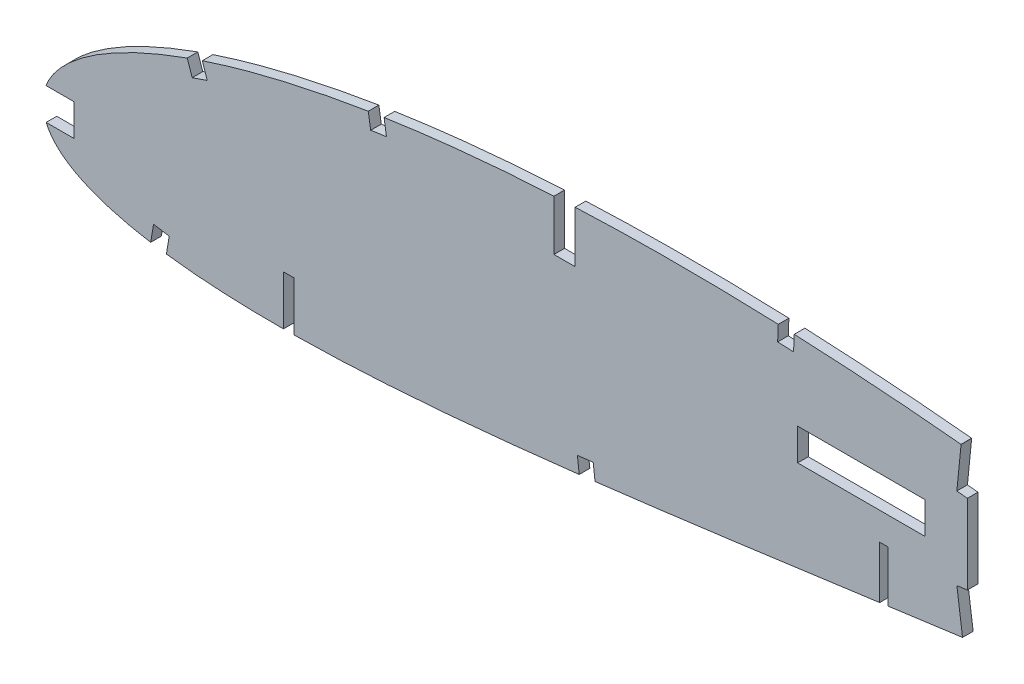
SolidWorks part; units mm, degrees
ref_plane "Front Plane" through (0, 0, 0) normal (0, 0, 1) x (1, 0, 0)
ref_plane "Top Plane" through (0, 0, 0) normal (0, 1, 0) x (1, 0, 0)
ref_plane "Right Plane" through (0, 0, 0) normal (1, 0, 0) x (0, 0, -1)
curve "Curve1"
  spline degree 3 poles (452.1031, 0.7048, 0) (452.0685, 0.7262, 0) (451.9301, 0.8117, 0) (451.6183, 1.003, 0) (451.099, 1.3216, 0) (450.372, 1.7653, 0) (449.438, 2.3329, 0) (448.2963, 3.0204, 0) (446.9478, 3.8257, 0) (445.3928, 4.7448, 0) (443.6314, 5.7736, 0) (441.6643, 6.9077, 0) (439.4916, 8.1409, 0) (437.1143, 9.468, 0) (434.5331, 10.8828, 0) (431.7485, 12.3789, 0) (428.7615, 13.9486, 0) (425.5733, 15.5853, 0) (422.1844, 17.2798, 0) (418.5964, 19.0251, 0) (414.8106, 20.8125, 0) (410.8282, 22.6325, 0) (406.6515, 24.4776, 0) (402.2816, 26.3365, 0) (397.7212, 28.201, 0) (392.972, 30.0605, 0) (388.0369, 31.9065, 0) (382.9178, 33.7272, 0) (377.6186, 35.5144, 0) (372.1418, 37.2567, 0) (366.4913, 38.9446, 0) (360.6704, 40.5671, 0) (354.684, 42.1159, 0) (348.5359, 43.5797, 0) (342.2312, 44.9487, 0) (335.775, 46.2147, 0) (329.1727, 47.3651, 0) (322.4425, 48.3989, 0) (315.6929, 49.2588, 0) (308.9571, 50.1023, 0) (302.2314, 50.8946, 0) (295.4235, 51.6533, 0) (288.5399, 52.3742, 0) (281.5875, 53.055, 0) (274.5733, 53.6928, 0) (267.5046, 54.2857, 0) (260.3883, 54.8303, 0) (253.2318, 55.3259, 0) (246.0422, 55.768, 0) (238.8272, 56.1563, 0) (231.5941, 56.4881, 0) (224.3504, 56.7611, 0) (217.1039, 56.9737, 0) (209.862, 57.1238, 0) (202.6326, 57.2105, 0) (195.4232, 57.2315, 0) (188.2416, 57.1863, 0) (181.0954, 57.0734, 0) (173.9924, 56.8912, 0) (166.9401, 56.6395, 0) (159.9462, 56.3182, 0) (153.0184, 55.9248, 0) (146.164, 55.4618, 0) (139.3909, 54.9271, 0) (132.7063, 54.3206, 0) (126.1174, 53.645, 0) (119.6314, 52.8983, 0) (113.2554, 52.0826, 0) (106.9962, 51.1996, 0) (100.8609, 50.2488, 0) (94.8561, 49.2329, 0) (88.9882, 48.153, 0) (83.2635, 47.0122, 0) (77.6882, 45.8109, 0) (72.2682, 44.5525, 0) (67.0092, 43.2395, 0) (61.9167, 41.874, 0) (56.9959, 40.4594, 0) (52.2519, 38.999, 0) (47.6902, 37.4943, 0) (43.3141, 35.951, 0) (39.1291, 34.3702, 0) (35.1384, 32.7568, 0) (31.3466, 31.113, 0) (27.7567, 29.4439, 0) (24.3726, 27.7512, 0) (21.1967, 26.0397, 0) (18.2324, 24.3122, 0) (15.4823, 22.5717, 0) (12.9477, 20.8227, 0) (10.632, 19.0664, 0) (8.5361, 17.307, 0) (6.6613, 15.5474, 0) (5.0102, 13.7886, 0) (3.5829, 12.0339, 0) (2.3811, 10.2847, 0) (1.4051, 8.5424, 0) (0.6571, 6.8085, 0) (0.1363, 5.084, 0) (-0.1488, 3.3712, 0) (-0.2197, 1.669, 0) (-0.0731, 0.5555, 0) (0, 0, 0) knots 0 0 0 0 0.000254 0.001015 0.002283 0.004057 0.006331 0.009105 0.012374 0.016134 0.02038 0.025106 0.030306 0.035972 0.0421 0.048678 0.055702 0.06316 0.071046 0.07935 0.088063 0.097176 0.106678 0.116562 0.126814 0.137428 0.148394 0.1597 0.171338 0.183298 0.19557 0.208144 0.221012 0.234162 0.247587 0.261277 0.275223 0.289414 0.303771 0.317689 0.331784 0.34604 0.360444 0.374983 0.38964 0.404403 0.419257 0.434187 0.449177 0.464215 0.479284 0.49437 0.509458 0.524532 0.539579 0.554583 0.56953 0.584403 0.599191 0.613877 0.628447 0.642889 0.657186 0.671326 0.685294 0.699078 0.712665 0.726043 0.739198 0.752118 0.764792 0.777208 0.789356 0.801224 0.812804 0.824083 0.835055 0.84571 0.856038 0.866034 0.875689 0.884998 0.893953 0.902553 0.910789 0.918661 0.926166 0.933303 0.940071 0.946475 0.952518 0.958205 0.963547 0.968557 0.97325 0.977651 0.981787 0.985694 0.989415 0.993001 0.996508 1 1 1 1
curve "Curve2"
  spline degree 3 poles (0, 0, 0) (0.1161, -0.5481, 0) (0.3488, -1.6467, 0) (0.9811, -3.2283, 0) (1.8173, -4.7487, 0) (2.8749, -6.2038, 0) (4.147, -7.5932, 0) (5.6306, -8.9184, 0) (7.3243, -10.1787, 0) (9.226, -11.3735, 0) (11.3328, -12.5041, 0) (13.6425, -13.5697, 0) (16.1528, -14.5701, 0) (18.8611, -15.5039, 0) (21.764, -16.3724, 0) (24.8588, -17.1737, 0) (28.1419, -17.9088, 0) (31.6103, -18.5759, 0) (35.26, -19.1755, 0) (39.0874, -19.7075, 0) (43.0885, -20.172, 0) (47.2594, -20.5682, 0) (51.596, -20.8969, 0) (56.0938, -21.1583, 0) (60.7487, -21.3533, 0) (65.556, -21.481, 0) (70.5112, -21.5436, 0) (75.6096, -21.5419, 0) (80.8464, -21.4754, 0) (86.2171, -21.3479, 0) (91.7164, -21.1586, 0) (97.3395, -20.9096, 0) (103.0813, -20.6036, 0) (108.9365, -20.2416, 0) (114.9002, -19.8251, 0) (120.967, -19.3576, 0) (127.1315, -18.8401, 0) (133.3883, -18.2757, 0) (139.7319, -17.6673, 0) (146.1567, -17.0167, 0) (152.6572, -16.327, 0) (159.2275, -15.6004, 0) (165.862, -14.8409, 0) (172.5546, -14.0497, 0) (179.2998, -13.2315, 0) (186.0911, -12.3877, 0) (192.923, -11.5217, 0) (199.7891, -10.6375, 0) (206.6832, -9.7349, 0) (213.5994, -8.8205, 0) (220.5311, -7.8935, 0) (227.4721, -6.9586, 0) (234.4161, -6.0188, 0) (241.3564, -5.0743, 0) (248.2868, -4.1291, 0) (255.2009, -3.1857, 0) (262.0918, -2.2442, 0) (268.9535, -1.3094, 0) (275.779, -0.3811, 0) (282.5619, 0.5389, 0) (289.2958, 1.4477, 0) (295.9744, 2.3443, 0) (302.5907, 3.228, 0) (309.138, 4.0992, 0) (315.5119, 4.9314, 0) (321.6955, 5.769, 0) (327.7099, 6.4556, 0) (333.6493, 7.0417, 0) (339.52, 7.5222, 0) (345.315, 7.9041, 0) (351.0275, 8.19, 0) (356.6509, 8.3839, 0) (362.1779, 8.4917, 0) (367.6017, 8.516, 0) (372.9148, 8.4647, 0) (378.1105, 8.3417, 0) (383.1813, 8.1528, 0) (388.1203, 7.9042, 0) (392.9205, 7.6027, 0) (397.5745, 7.2527, 0) (402.076, 6.8625, 0) (406.4179, 6.4377, 0) (410.5937, 5.9833, 0) (414.5972, 5.5086, 0) (418.4221, 5.0169, 0) (422.0625, 4.5163, 0) (425.5126, 4.0117, 0) (428.7669, 3.5097, 0) (431.8204, 3.015, 0) (434.6681, 2.5342, 0) (437.3055, 2.0718, 0) (439.7281, 1.6323, 0) (441.9324, 1.2212, 0) (443.9143, 0.8406, 0) (445.6709, 0.4968, 0) (447.199, 0.1913, 0) (448.4964, -0.0716, 0) (449.5609, -0.2909, 0) (450.3908, -0.463, 0) (450.9844, -0.5881, 0) (451.3411, -0.6626, 0) (451.4997, -0.6964, 0) (451.5393, -0.7048, 0) knots 0 0 0 0 0.003638 0.007293 0.011028 0.014901 0.018963 0.023258 0.027821 0.032679 0.037853 0.043362 0.049215 0.055422 0.061989 0.068918 0.076211 0.083868 0.091887 0.100266 0.109 0.118085 0.127515 0.137285 0.147388 0.157816 0.168563 0.179619 0.190977 0.202627 0.21456 0.226767 0.239236 0.251959 0.264924 0.27812 0.291536 0.30516 0.318981 0.332985 0.347163 0.361499 0.375981 0.390597 0.405333 0.420175 0.43511 0.450124 0.465203 0.480333 0.495501 0.51069 0.525887 0.541078 0.556247 0.571382 0.586466 0.601485 0.616424 0.631269 0.646007 0.660621 0.675098 0.689423 0.703582 0.716908 0.730009 0.742952 0.755726 0.76832 0.780724 0.792927 0.804916 0.816679 0.828204 0.839475 0.850481 0.861208 0.871639 0.881763 0.891564 0.901027 0.910139 0.918884 0.927249 0.935221 0.942785 0.949928 0.956638 0.962904 0.968712 0.974054 0.978918 0.983297 0.98718 0.990561 0.993433 0.995791 0.99763 0.998946 0.999737 1 1 1 1
sketch "Sketch1" plane through (0, 0, 0) normal (0, 0, 1) x (1, 0, 0)
  line L24 (435.3301, 0.6787) -> (439.1729, -1.6142)
  line L25 (434.7872, -0.6787) -> (439.1729, -1.6142)
  spline S4 degree 3 poles (0, 0) (0.1118, -0.5277) (0.3359, -1.5856) (0.9447, -3.1085) (1.7499, -4.5725) (2.7683, -5.9736) (3.9931, -7.3115) (5.4217, -8.5876) (7.0526, -9.8011) (8.8837, -10.9516) (10.9124, -12.0402) (13.1363, -13.0663) (15.5535, -14.0296) (18.1613, -14.9287) (20.9565, -15.765) (23.9365, -16.5366) (27.0978, -17.2444) (30.4375, -17.8867) (33.9519, -18.4641) (37.6373, -18.9763) (41.49, -19.4236) (45.5061, -19.8051) (49.6818, -20.1216) (54.0128, -20.3734) (58.4949, -20.5611) (63.1239, -20.6841) (67.8952, -20.7443) (72.8045, -20.7427) (77.847, -20.6787) (83.0184, -20.5559) (88.3137, -20.3736) (93.7282, -20.1339) (99.2569, -19.8392) (104.895, -19.4906) (110.6374, -19.0896) (116.4791, -18.6394) (122.4149, -18.1411) (128.4396, -17.5977) (134.5478, -17.0118) (140.7343, -16.3853) (146.9936, -15.7212) (153.3201, -15.0216) (159.7085, -14.2903) (166.1528, -13.5285) (172.6478, -12.7406) (179.1872, -11.9281) (185.7655, -11.0942) (192.377, -10.2428) (199.0153, -9.3738) (205.6749, -8.4933) (212.3494, -7.6007) (219.0329, -6.7005) (225.7193, -5.7955) (232.4021, -4.886) (239.0753, -3.9759) (245.7329, -3.0675) (252.3682, -2.161) (258.9753, -1.2608) (265.5476, -0.3669) (272.0789, 0.5189) (278.563, 1.394) (284.9937, 2.2573) (291.3645, 3.1082) (297.669, 3.9471) (303.8064, 4.7484) (309.7606, 5.555) (315.5518, 6.2161) (321.2709, 6.7805) (326.9238, 7.2431) (332.5038, 7.6108) (338.0044, 7.8861) (343.4191, 8.0729) (348.7411, 8.1767) (353.9637, 8.2001) (359.0797, 8.1506) (364.0826, 8.0323) (368.9653, 7.8503) (373.7211, 7.6109) (378.3431, 7.3206) (382.8245, 6.9836) (387.159, 6.6079) (391.3398, 6.1989) (395.3607, 5.7613) (399.2157, 5.3043) (402.8986, 4.8308) (406.404, 4.3487) (409.7261, 3.8629) (412.8597, 3.3795) (415.7999, 2.9031) (418.5419, 2.4402) (421.0815, 1.9949) (423.4142, 1.5717) (425.5368, 1.1759) (427.445, 0.8095) (429.1365, 0.4784) (430.6079, 0.1842) (431.8572, -0.0689) (432.8822, -0.2801) (433.6813, -0.4458) (434.2529, -0.5663) (434.5964, -0.638) (434.749, -0.6706) (434.7872, -0.6787) knots 0 0 0 0 0.003638 0.007293 0.011028 0.014901 0.018963 0.023258 0.027821 0.032679 0.037853 0.043362 0.049215 0.055422 0.061989 0.068918 0.076211 0.083868 0.091887 0.100266 0.109 0.118085 0.127515 0.137285 0.147388 0.157816 0.168563 0.179619 0.190977 0.202627 0.21456 0.226767 0.239236 0.251959 0.264924 0.27812 0.291536 0.30516 0.318981 0.332985 0.347163 0.361499 0.375981 0.390597 0.405333 0.420175 0.43511 0.450124 0.465203 0.480333 0.495501 0.51069 0.525887 0.541078 0.556247 0.571382 0.586466 0.601485 0.616424 0.631269 0.646007 0.660621 0.675098 0.689423 0.703582 0.716908 0.730009 0.742952 0.755726 0.76832 0.780724 0.792927 0.804916 0.816679 0.828204 0.839475 0.850481 0.861208 0.871639 0.881763 0.891564 0.901027 0.910139 0.918884 0.927249 0.935221 0.942785 0.949928 0.956638 0.962904 0.968712 0.974054 0.978918 0.983297 0.98718 0.990561 0.993433 0.995791 0.99763 0.998946 0.999737 1 1 1 1
  spline S5 degree 3 poles (435.3301, 0.6787) (435.2968, 0.6993) (435.1635, 0.7816) (434.8632, 0.9658) (434.3632, 1.2726) (433.6632, 1.6998) (432.7638, 2.2463) (431.6645, 2.9084) (430.3661, 3.6837) (428.8687, 4.5688) (427.1727, 5.5594) (425.2785, 6.6514) (423.1865, 7.8389) (420.8974, 9.1168) (418.4119, 10.4791) (415.7306, 11.9197) (412.8545, 13.4311) (409.7845, 15.0071) (406.5213, 16.6387) (403.0665, 18.3192) (399.4211, 20.0403) (395.5865, 21.7928) (391.5647, 23.5695) (387.357, 25.3594) (382.9657, 27.1547) (378.3927, 28.9452) (373.6407, 30.7228) (368.7116, 32.4759) (363.609, 34.1968) (358.3353, 35.8745) (352.8945, 37.4998) (347.2896, 39.0621) (341.5252, 40.5534) (335.6052, 41.9629) (329.5344, 43.2811) (323.3177, 44.5002) (316.9603, 45.6079) (310.4799, 46.6033) (303.9807, 47.4313) (297.4948, 48.2435) (291.0186, 49.0064) (284.4633, 49.737) (277.8351, 50.4311) (271.1406, 51.0867) (264.3866, 51.7008) (257.5802, 52.2717) (250.7279, 52.7961) (243.8369, 53.2733) (236.914, 53.699) (229.9667, 54.0729) (223.0019, 54.3924) (216.027, 54.6553) (209.0493, 54.86) (202.0761, 55.0045) (195.1149, 55.088) (188.173, 55.1082) (181.2578, 55.0647) (174.3767, 54.956) (167.5373, 54.7806) (160.7467, 54.5381) (154.0122, 54.2288) (147.3414, 53.85) (140.7414, 53.4041) (134.2195, 52.8893) (127.7829, 52.3053) (121.4385, 51.6548) (115.1931, 50.9357) (109.0536, 50.1503) (103.0266, 49.3001) (97.119, 48.3846) (91.3369, 47.4064) (85.6868, 46.3665) (80.1745, 45.2681) (74.806, 44.1113) (69.5871, 42.8996) (64.5231, 41.6353) (59.6196, 40.3205) (54.8814, 38.9584) (50.3134, 37.5521) (45.9209, 36.1032) (41.7071, 34.6172) (37.6774, 33.0951) (33.8348, 31.5415) (30.1837, 29.9587) (26.7269, 28.3515) (23.4684, 26.7216) (20.4104, 25.0737) (17.5559, 23.4102) (14.9079, 21.7343) (12.4673, 20.0502) (10.2376, 18.359) (8.2194, 16.6649) (6.4142, 14.9706) (4.8244, 13.2771) (3.45, 11.5875) (2.2928, 9.9031) (1.353, 8.2255) (0.6327, 6.5559) (0.1312, 4.8953) (-0.1433, 3.2462) (-0.2116, 1.607) (-0.0704, 0.5349) (0, 0) knots 0 0 0 0 0.000254 0.001015 0.002283 0.004057 0.006331 0.009105 0.012374 0.016134 0.02038 0.025106 0.030306 0.035972 0.0421 0.048678 0.055702 0.06316 0.071046 0.07935 0.088063 0.097176 0.106678 0.116562 0.126814 0.137428 0.148394 0.1597 0.171338 0.183298 0.19557 0.208144 0.221012 0.234162 0.247587 0.261277 0.275223 0.289414 0.303771 0.317689 0.331784 0.34604 0.360444 0.374983 0.38964 0.404403 0.419257 0.434187 0.449177 0.464215 0.479284 0.49437 0.509458 0.524532 0.539579 0.554583 0.56953 0.584403 0.599191 0.613877 0.628447 0.642889 0.657186 0.671326 0.685294 0.699078 0.712665 0.726043 0.739198 0.752118 0.764792 0.777208 0.789356 0.801224 0.812804 0.824083 0.835055 0.84571 0.856038 0.866034 0.875689 0.884998 0.893953 0.902553 0.910789 0.918661 0.926166 0.933303 0.940071 0.946475 0.952518 0.958205 0.963547 0.968557 0.97325 0.977651 0.981787 0.985694 0.989415 0.993001 0.996508 1 1 1 1
extrude "Boss-Extrude1" add sketch "Sketch1" along normal blind 3.175
sketch "Sketch2" plane through (0, 0, 0) normal (0, 0, -1) x (-1, 0, 0)
  line L0 (-252.7944, 13.2215) -> (-250.2544, 13.2215)
  line L1 (-250.2544, -2.1152) -> (-250.2544, -3.9863)
  line L2 (-252.7944, 13.2215) -> (-252.7944, -2.1152)
  line L4 (-250.2544, -3.9863) -> (-252.7944, -3.0508)
  line L5 (-252.7944, -3.0508) -> (-252.7944, -2.1152)
  line L7 (-159.1319, 54.4222) -> (-159.1319, 39.0391)
  line L8 (-159.1319, 39.0391) -> (-152.7819, 39.0391)
  line L9 (-152.7819, 54.4222) -> (-152.7819, 57.6454)
  line L10 (-74.9944, -5.9288) -> (-74.9944, -20.1418)
  line L12 (-152.7819, 57.6454) -> (-159.1319, 55.5409)
  line L13 (-159.1319, 55.5409) -> (-159.1319, 54.4222)
  line L14 (-71.8194, -5.9288) -> (-71.8194, -20.1418)
  line L16 (-74.9944, -5.9288) -> (-71.8194, -5.9288)
  line L17 (-71.8194, -20.1418) -> (-71.8194, -22.1459)
  line L19 (-152.7819, 54.4222) -> (-152.7819, 39.0391)
  line L20 (-71.8194, -22.1459) -> (-74.9944, -20.9764)
  line L21 (-74.9944, -20.9764) -> (-74.9944, -20.1418)
  line L22 (-250.2544, 13.2215) -> (-250.2544, -2.1152)
extrude "Cut-Extrude1" cut sketch "Sketch2" against normal blind 7.62
sketch "Sketch3" plane through (0, 0, 0) normal (0, 0, -1) x (-1, 0, 0)
  circle A1 centre (-292.3838, 26.2554) radius 6.35
extrude "Cut-Extrude2" cut sketch "Sketch3" against normal blind 7.62
sketch "Sketch4" plane through (0, 0, 3.175) normal (0, 0, 1) x (1, 0, 0)
  line L0 (274.6066, 50.6647) -> (273.3497, 38.0281)
  line L1 (274.6066, 50.6647) -> (273.3497, 38.0281)
  line L2 (276.5088, 37.7139) -> (277.7874, 50.3428)
  line L3 (276.5088, 37.7139) -> (277.7874, 50.3428)
  line L4 (278.2022, 1.3477) -> (276.5088, 13.9346)
  line L5 (278.2022, 1.3477) -> (276.5088, 13.9346)
  line L6 (273.3622, 13.5108) -> (275.0576, 0.9245)
  line L7 (273.3622, 13.5108) -> (275.0576, 0.9245)
  line L8 (224.4836, 49.6431) -> (224.6991, 54.396)
  line L9 (224.4836, 49.6431) -> (224.6991, 54.396)
  line L10 (165.0827, -13.6872) -> (164.5226, -8.9534)
  line L11 (165.0827, -13.6872) -> (164.5226, -8.9534)
  line L12 (102.6454, 44.5104) -> (101.9324, 49.2278)
  line L13 (102.6454, 44.5104) -> (101.9324, 49.2278)
  line L14 (36.8388, -18.5812) -> (37.6418, -13.8082)
  line L15 (36.8388, -18.5812) -> (37.6418, -13.8082)
  line L16 (49.0205, 32.2539) -> (47.492, 36.7462)
  line L17 (49.0205, 32.2539) -> (47.492, 36.7462)
  line L18 (9.0835, -2.7147) -> (9.0835, 6.8103)
  line L19 (9.0835, -2.7147) -> (9.0835, 6.8103)
  line L20 (-0.4415, 6.8103) -> (9.0835, 6.8103)
  line L21 (-0.4415, 6.8103) -> (9.0835, 6.8103)
  line L22 (32.9524, -13.0236) -> (32.1659, -17.7312)
  line L23 (32.9524, -13.0236) -> (32.1659, -17.7312)
  line L24 (97.1897, 48.4826) -> (97.9364, 43.7986)
  line L25 (97.1897, 48.4826) -> (97.9364, 43.7986)
  line L26 (159.7931, -9.5131) -> (160.3442, -14.2455)
  line L27 (159.7931, -9.5131) -> (160.3442, -14.2455)
  line L28 (42.9896, 35.1929) -> (44.512, 30.7197)
  line L29 (42.9896, 35.1929) -> (44.512, 30.7197)
  line L30 (-0.4415, -2.7147) -> (9.0835, -2.7147)
  line L31 (-0.4415, -2.7147) -> (9.0835, -2.7147)
  line L32 (219.9134, 54.5992) -> (219.7258, 49.8498)
  line L33 (219.9134, 54.5992) -> (219.7258, 49.8498)
  line L34 (276.5088, 13.9346) -> (276.5088, 37.7139)
  line L35 (273.3497, 38.0281) -> (276.5088, 37.7139)
  line L36 (276.5088, 13.9346) -> (273.3622, 13.5108)
  line L37 (275.0576, 0.9245) -> (278.2022, 1.3477)
  line L38 (219.7258, 49.8498) -> (224.4836, 49.6431)
  line L39 (224.6991, 54.396) -> (219.9134, 54.5992)
  line L40 (159.7931, -9.5131) -> (164.5226, -8.9534)
  line L41 (165.0827, -13.6872) -> (160.3442, -14.2455)
  line L42 (42.9896, 35.1929) -> (47.492, 36.7462)
  line L43 (44.512, 30.7197) -> (49.0205, 32.2539)
  line L44 (97.1897, 48.4826) -> (101.9324, 49.2278)
  line L45 (102.6454, 44.5104) -> (97.9364, 43.7986)
  line L46 (-0.4415, 6.8103) -> (-0.4415, -2.7147)
  line L47 (32.9524, -13.0236) -> (37.6418, -13.8082)
  line L48 (36.8388, -18.5812) -> (32.1659, -17.7312)
  line L49 (277.7874, 50.3428) -> (274.6066, 50.6647)
  line L50 (275.0576, 0.9245) -> (275.0576, -18.8331)
  line L51 (225.7088, 31.0179) -> (263.8088, 31.0179)
  line L52 (225.7088, 31.0179) -> (225.7088, 21.4929)
  line L53 (225.7088, 21.4929) -> (263.8088, 21.4929)
  line L54 (263.8088, 31.0179) -> (263.8088, 21.4929)
  line L55 (446.0862, 59.9441) -> (446.0862, -18.8331)
  line L56 (446.0862, -18.8331) -> (275.0576, -18.8331)
  line L57 (274.6066, 50.6647) -> (274.6066, 59.9441)
  line L58 (274.6066, 59.9441) -> (446.0862, 59.9441)
  line L59 (32.1659, -17.7312) -> (31.5691, -21.3035)
  line L60 (31.5691, -21.3035) -> (36.2028, -22.0776)
  line L61 (36.2028, -22.0776) -> (36.8388, -18.5812)
  circle A0 centre (292.3838, 26.2554) radius 6.35 construction
  circle A1 centre (292.3838, 26.2554) radius 6.35
  point P40 (263.8088, 26.2554)
  dimension "D1" = 9.525
  dimension "D2" = 38.1
  dimension "D3" = 12.7
extrude "Cut-Extrude3" cut sketch "Sketch4" against normal through all contours L31 L19 L21 | L29 L43 L17 | L48 L15 L47 L23 | L45 L13 L25 | L40 L27 L11 | L33 L38 L9 | L54 L51 L52 L53 | L3 L49 L1 L35 | L3 L34 L5 | L7 L37 L5 L36 | L60 L61 L59 | L61 L48 L59 region at (275.5637, 44.1947, 3.175) region at (361.7755, 20.4803, 3.175) region at (275.7826, 7.4301, 3.175) region at (222.206, 52.1243, 3.175) region at (162.4359, -11.6005, 3.175) region at (99.9278, 46.5083, 3.175) region at (34.9052, -15.7866, 3.175) region at (34.1874, -19.9188, 3.175) region at (46.0051, 33.7288, 3.175) region at (4.321, 2.0478, 3.175) region at (244.7588, 26.2554, 3.175)
move or copy body "Body-Move/Copy1" [suppressed] bodies to move or copy 118 119 parameters "D1"=0, "D2"=0, "D3"=0
